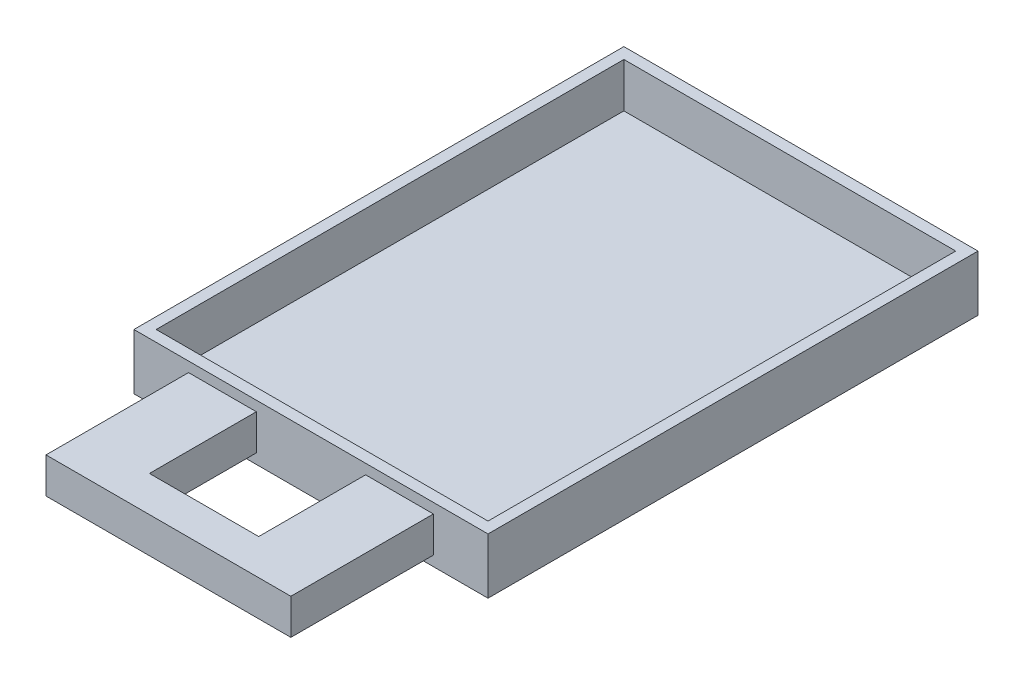
SolidWorks part; units mm, degrees
ref_plane "Front Plane" through (0, 0, 0) normal (0, 0, 1) x (1, 0, 0)
ref_plane "Top Plane" through (0, 0, 0) normal (0, 1, 0) x (1, 0, 0)
ref_plane "Right Plane" through (0, 0, 0) normal (1, 0, 0) x (0, 0, -1)
sketch "Sketch1" plane through (0, 0, 0) normal (0, 0, 1) x (1, 0, 0)
  line L0 (-79.5, 0) -> (79.5, 0)
  line L1 (79.5, 0) -> (79.5, 25)
  line L2 (79.5, 25) -> (-79.5, 25)
  line L3 (-79.5, 25) -> (-79.5, 0)
  dimension "D1" = 159
  dimension "D2" = 25
extrude "Boss-Extrude1" add sketch "Sketch1" along normal blind 220
sketch "Sketch2" plane through (0, 25, 0) normal (0, 1, 0) x (1, 0, 0)
  line L0 (0, 0) -> (0, -220) construction
  line L1 (79.5, -220) -> (-79.5, -220) construction
  line L2 (-79.5, -110) -> (79.5, -110) construction
  line L3 (-79.5, -220) -> (-79.5, 0) construction
  line L4 (79.5, -220) -> (79.5, 0) construction
  line L5 (-74.5, -5) -> (74.5, -5)
  line L6 (74.5, -5) -> (74.5, -215)
  line L7 (74.5, -215) -> (-74.5, -215)
  line L8 (-74.5, -215) -> (-74.5, -5)
  line L9 (79.5, 0) -> (-79.5, 0) construction
  dimension "D1" = 5
  dimension "D2" = 5
  dimension "D3" = 5
  dimension "D4" = 5
extrude "Cut-Extrude1" cut sketch "Sketch2" against normal blind 20
sketch "Sketch3" plane through (0, 0, 220) normal (0, 0, 1) x (1, 0, 0)
  line L0 (0, 25) -> (0, 0) construction
  line L1 (79.5, 25) -> (-79.5, 25) construction
  line L2 (-79.5, 12.5) -> (0, 12.5) construction
  line L3 (-79.5, 25) -> (-79.5, 0) construction
  line L4 (-79.5, 0) -> (79.5, 0) construction
  line L10 (-54.97, 20.5) -> (-24.53, 20.5)
  line L11 (-24.53, 20.5) -> (-24.53, 4.5)
  line L12 (-24.53, 4.5) -> (-54.97, 4.5)
  line L13 (-54.97, 4.5) -> (-54.97, 20.5)
  dimension "D1" = 4.5
  dimension "D2" = 4.5
  dimension "D3" = 24.53
  dimension "D4" = 24.53
extrude "Boss-Extrude2" add sketch "Sketch3" along normal blind 64
ref_axis "Axis1" through (0, 25, 220) along (0, -1, 0)
ref_plane "Plane1" through (0, 0, 0) normal (1, 0, 0) x (0, 0, -1)
mirror "Mirror1" about plane through (0, 0, 0) normal (1, 0, 0) of "Boss-Extrude2"
sketch "Sketch4" plane through (-24.53, 0, 0) normal (1, 0, 0) x (0, 0, -1)
  line L0 (-268, 20.5) -> (-268, 4.5)
  line L1 (-284, 20.5) -> (-220, 20.5) construction
  line L2 (-284, 4.5) -> (-220, 4.5) construction
  line L3 (-268, 4.5) -> (-284, 4.5)
  line L4 (-284, 4.5) -> (-284, 20.5)
  line L5 (-284, 20.5) -> (-268, 20.5)
  dimension "D1" = 16
extrude "Boss-Extrude3" add sketch "Sketch4" along normal up to next
